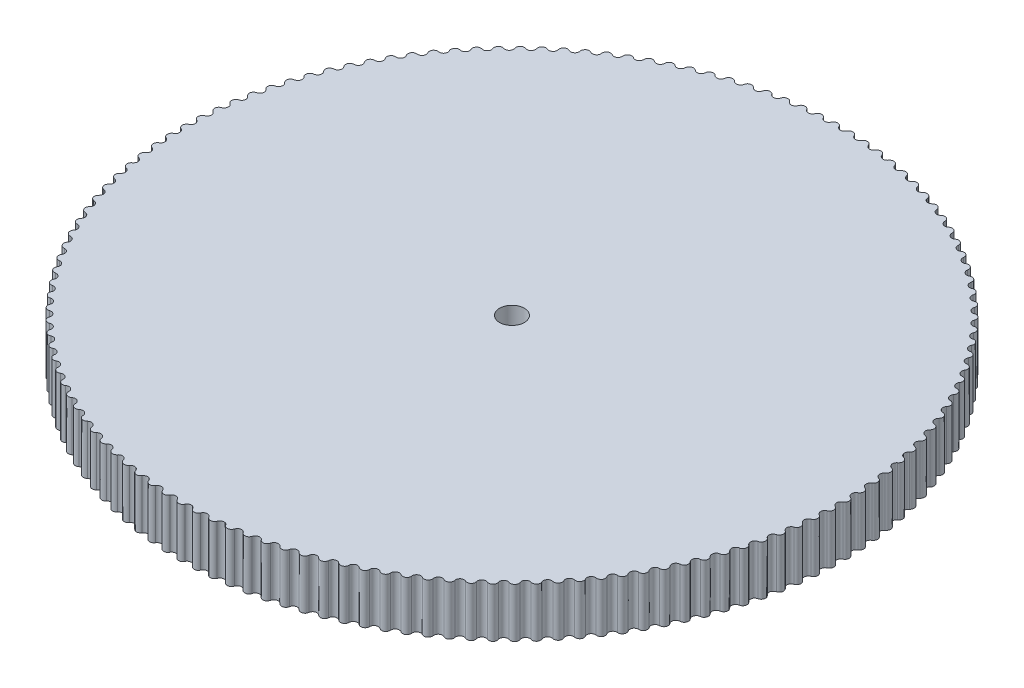
SolidWorks part; units mm, degrees
note: '?' marks a value the reader was unsure of.
ref_plane "Front Plane" through (0, 0, 0) normal (0, 0, 1) x (1, 0, 0)
ref_plane "Top Plane" through (0, 0, 0) normal (0, 1, 0) x (1, 0, 0)
ref_plane "Right Plane" through (0, 0, 0) normal (1, 0, 0) x (0, 0, -1)
sketch "Sketch1" plane through (0, 0, 0) normal (0, 1, 0) x (1, 0, 0)
  line L0 (0, 131) -> (0, 133) construction
  line L1 (3.0941, 130.9635) -> (3.1413, 132.9629) construction
  line L2 (6.1864, 130.8538) -> (6.2808, 132.8516) construction
  line L3 (0, 132) -> (0, 5)
  line L4 (0.2361, 4.9944) -> (6.2336, 131.8527)
  circle A0 centre (0, 0) radius 131 construction
  arc A1 (0, 132) -> (3.1177, 131.9632) centre (1.5675, 132.7126) ccw
  arc A2 (6.2808, 132.8516) -> (0, 133) centre (0, 0) ccw construction
  arc A3 (3.1177, 131.9632) -> (6.2336, 131.8527) centre (4.6509, 131.2089) cw
  arc A4 (0.2361, 4.9944) -> (0, 5) centre (0, 0) ccw
  point P6 (0, 132)
  point P9 (3.1177, 131.9632)
  dimension "D1" = 262
  dimension "D2" = 2
  dimension "D3" = 10
extrude "Boss-Extrude1" add sketch "Sketch1" along normal blind 20
pattern_circular "CirPattern1" count 133 over 360 about axis through (0, 0, 0) along (0, 1, 0) of "Boss-Extrude1"
ref_axis "Axis1" through (0, 0, 0) along (0, 1, 0)?
sketch "Sketch2" plane through (0, 20, 0) normal (0, 1, 0) x (1, 0, 0)
  line L0 (0, 74.1691) -> (0, -78.0459) construction
  line L1 (19.05, 12.7) -> (26.67, 12.7)
  line L2 (19.05, 12.7) -> (19.05, -12.7)
  line L3 (19.05, -12.7) -> (26.67, -12.7)
  line L4 (26.67, 12.7) -> (26.67, -12.7)
  line L5 (-26.67, 12.7) -> (-26.67, -12.7)
  line L6 (-19.05, -12.7) -> (-26.67, -12.7)
  line L7 (-19.05, 12.7) -> (-19.05, -12.7)
  line L8 (-19.05, 12.7) -> (-26.67, 12.7)
  point P6 (19.05, 0)
  point P12 (-19.05, 0)
  dimension "D1" = 7.62
  dimension "D2" = 25.4
  dimension "D3" = 19.05
